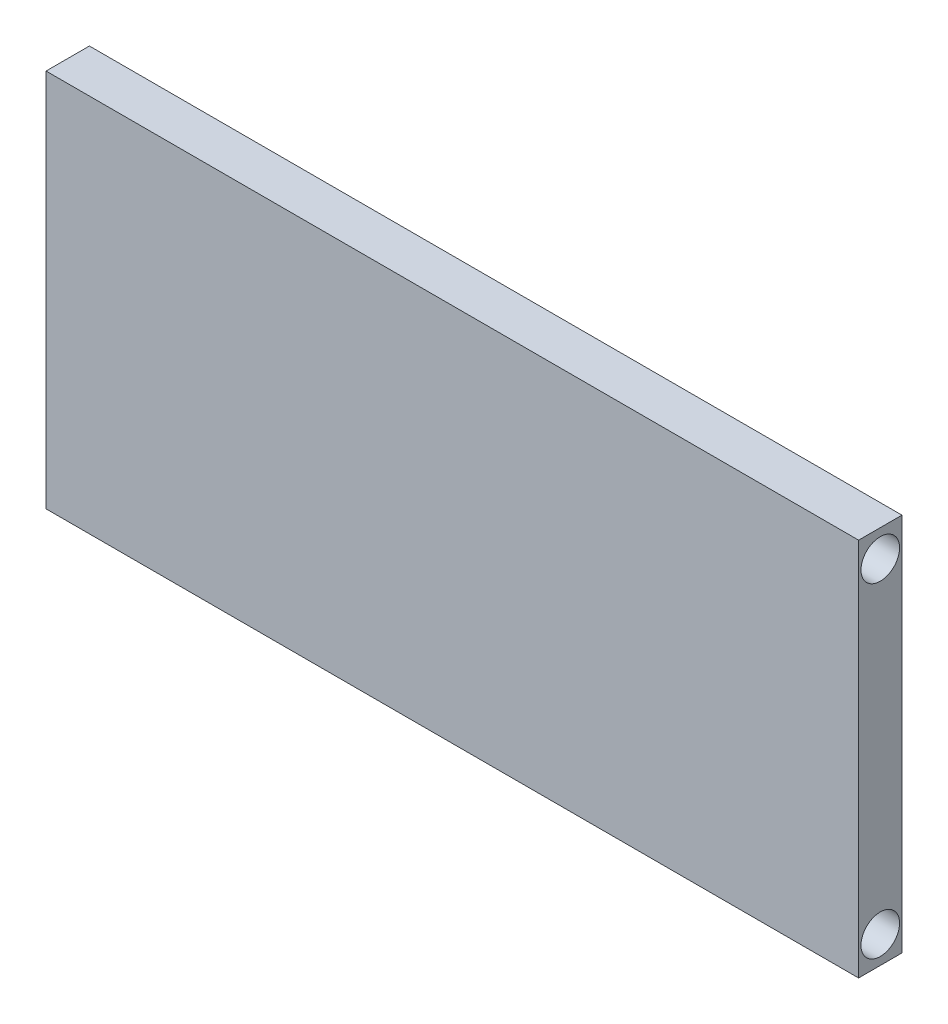
SolidWorks part; units mm, degrees
ref_plane "前视基准面" through (0, 0, 0) normal (0, 0, 1) x (1, 0, 0)
ref_plane "上视基准面" through (0, 0, 0) normal (0, 1, 0) x (1, 0, 0)
ref_plane "右视基准面" through (0, 0, 0) normal (1, 0, 0) x (0, 0, -1)
sketch "board" plane through (0, 0, 0) normal (0, 0, 1) x (1, 0, 0)
  line L0 (-76.2, 0) -> (76.2, 0) construction
  line L1 (76.2, -35.56) -> (-76.2, -35.56)
  line L2 (76.2, -35.56) -> (76.2, 35.56)
  line L3 (76.2, 35.56) -> (-76.2, 35.56)
  line L4 (-76.2, -35.56) -> (-76.2, 35.56)
  line L5 (76.2, -35.56) -> (-76.2, 35.56) construction
  line L6 (76.2, 35.56) -> (-76.2, -35.56) construction
  point P0 (0, 0)
  dimension "D1" = 152.4
  dimension "D2" = 71.12
extrude "Boss-Extrude1" add sketch "board" along normal blind 4.064 and the other way blind 4.064
sketch "Sketch2" plane through (76.2, 0, 0) normal (1, 0, 0) x (0, 0, -1)
  line L0 (0, 35.56) -> (0, -35.56) construction
  line L1 (4.064, 35.56) -> (-4.064, 35.56) construction
  line L2 (4.064, -35.56) -> (-4.064, -35.56) construction
  line L3 (4.064, 0) -> (-4.064, 0) construction
  line L4 (4.064, -35.56) -> (4.064, 35.56) construction
  line L5 (-4.064, -35.56) -> (-4.064, 35.56) construction
  circle A0 centre (0, 30.48) radius 3.6195
  circle A1 centre (0, -30.48) radius 3.6195
  point P6 (0, 0)
  point P16 (0, 0)
  dimension "D2" = 7.239
  dimension "D1" = 30.48
extrude "Cut-Extrude1" cut sketch "Sketch2" against normal through all
